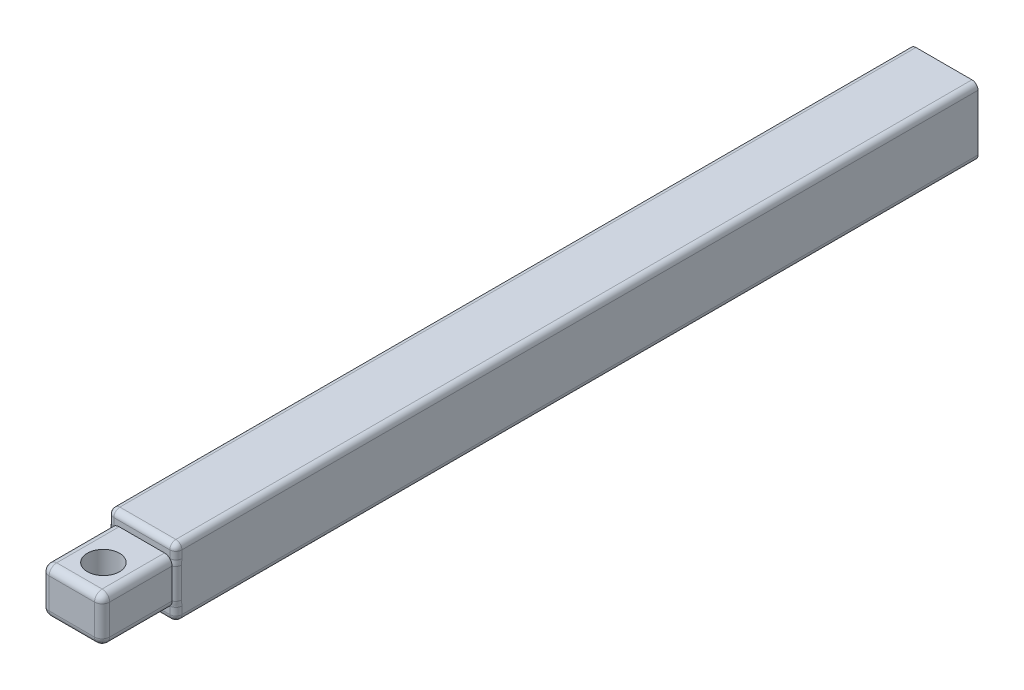
SolidWorks part; units mm, degrees
ref_plane "Plan de face" through (0, 0, 0) normal (0, 0, 1) x (1, 0, 0)
ref_plane "Plan de dessus" through (0, 0, 0) normal (0, 1, 0) x (1, 0, 0)
ref_plane "Plan de droite" through (0, 0, 0) normal (1, 0, 0) x (0, 0, -1)
sketch "Esquisse1" plane through (0, 0, 0) normal (0, 0, 1) x (1, 0, 0)
  line L1 (-0.2602, -0.3903) -> (8.7398, -0.3903)
  line L2 (-0.2602, -0.3903) -> (-0.2602, 8.6097)
  line L3 (-0.2602, 8.6097) -> (8.7398, 8.6097)
  line L4 (8.7398, -0.3903) -> (8.7398, 8.6097)
  dimension "D1" = 9
  dimension "D2" = 9
extrude "Extrusion1" add sketch "Esquisse1" along normal blind 106
sketch "Esquisse2" plane through (0, 0, 106) normal (0, 0, 1) x (1, 0, 0)
  line L1 (0.2398, 7.1097) -> (8.2398, 7.1097)
  line L2 (0.2398, 7.1097) -> (0.2398, 1.1097)
  line L3 (0.2398, 1.1097) -> (8.2398, 1.1097)
  line L4 (8.2398, 7.1097) -> (8.2398, 1.1097)
  line L5 (-0.2602, 8.6097) -> (-0.2602, -0.3903) construction
  line L6 (-0.2602, -0.3903) -> (8.7398, -0.3903) construction
  dimension "D1" = 6
  dimension "D2" = 8
  dimension "D3" = 0.5
  dimension "D4" = 7.5
extrude "Extrusion2" add sketch "Esquisse2" along normal blind 9.25
fillet "Congé1" radius 1 8 edges at (8.2398, 7.1097, 110.625) (8.2398, 1.1097, 110.625) (0.2398, 1.1097, 110.625) (8.2398, 4.1097, 115.25) (4.2398, 1.1097, 115.25) (0.2398, 4.1097, 115.25) (4.2398, 7.1097, 115.25) (0.2398, 7.1097, 110.625)
sketch "Esquisse4" plane through (0, 7.1097, 0) normal (0, 1, 0) x (-1, 0, 0)
  line L1 (-7.2398, 106) -> (-1.2398, 106) construction
  line L2 (-8.2398, 106) -> (-8.2398, 114.25) construction
  circle A0 centre (-4.2898, 111.125) radius 2.125
  dimension "D1" = 3.95
  dimension "D2" = 5.125
extrude "Enlèv. mat.-Extru.2" cut sketch "Esquisse4" against normal blind 16
fillet "Congé2" radius 0.8 8 edges at (8.7398, 4.1097, 106) (4.2398, 8.6097, 106) (-0.2602, 4.1097, 106) (4.2398, -0.3903, 106) (8.7398, 8.6097, 53) (-0.2602, 8.6097, 53) (-0.2602, -0.3903, 53) (8.7398, -0.3903, 53)
